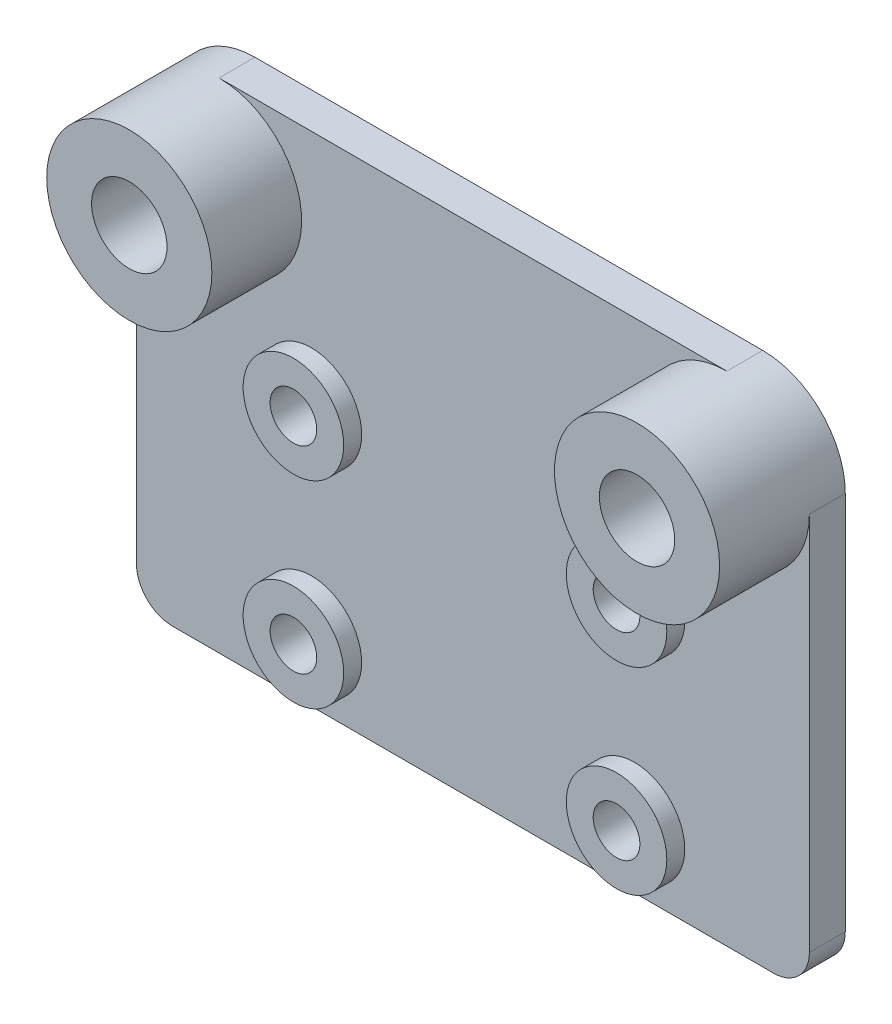
SolidWorks part; units mm, degrees
ref_plane "Plan de face" through (0, 0, 0) normal (0, 0, 1) x (1, 0, 0)
ref_plane "Plan de dessus" through (0, 0, 0) normal (0, 1, 0) x (1, 0, 0)
ref_plane "Plan de droite" through (0, 0, 0) normal (1, 0, 0) x (0, 0, -1)
sketch "Esquisse1" plane through (0, 0, 0) normal (0, 0, 1) x (1, 0, 0)
  line L0 (-14.1421, 14.1421) -> (14.1421, 14.1421) construction
  line L1 (9, 5.5) -> (-9, 5.5) construction
  line L2 (9, 5.5) -> (9, -5.5) construction
  line L3 (9, -5.5) -> (-9, -5.5) construction
  line L4 (-9, 5.5) -> (-9, -5.5) construction
  line L5 (9, 5.5) -> (-9, -5.5) construction
  line L6 (9, -5.5) -> (-9, 5.5) construction
  line L7 (14.1421, 14.1421) -> (14.1421, -14.1421) construction
  line L8 (14.1421, -14.1421) -> (-14.1421, -14.1421) construction
  line L9 (-14.1421, -14.1421) -> (-14.1421, 14.1421) construction
  circle A0 centre (0, 0) radius 20 construction
  circle A1 centre (-14.1421, 14.1421) radius 2.1
  circle A2 centre (14.1421, 14.1421) radius 2.1
  circle A3 centre (14.1421, -14.1421) radius 2.1 construction
  circle A4 centre (-14.1421, -14.1421) radius 2.1 construction
  circle A5 centre (0, 0) radius 25
  circle A6 centre (-9, 5.5) radius 1.3
  circle A7 centre (-9, -5.5) radius 1.3
  circle A8 centre (9, 5.5) radius 1.3
  circle A9 centre (9, -5.5) radius 1.3
  point P0 (0, 0)
  dimension "D3" = 40
  dimension "D4" = 4.2
  dimension "D5" = 4.2
  dimension "D6" = 4.2
  dimension "D7" = 4.2
  dimension "D8" = 50
  dimension "D9" = 2.6
  dimension "D10" = 2.6
  dimension "D11" = 2.6
  dimension "D12" = 2.6
  dimension "D1" = 18
  dimension "D2" = 11
extrude "Boss.-Extru.1" add sketch "Esquisse1" along normal blind 2
sketch "Esquisse2" plane through (0, 0, 2) normal (0, 0, 1) x (1, 0, 0)
  line L0 (0, -14) -> (0, 0) construction
  line L1 (11, -19) -> (-11, -19)
  line L2 (11, -19) -> (11, -9)
  line L3 (11, -9) -> (-11, -9)
  line L4 (-11, -19) -> (-11, -9)
  line L5 (11, -19) -> (-11, -9) construction
  line L6 (11, -9) -> (-11, -19) construction
  point P0 (0, -14)
  dimension "D1" = 9
  dimension "D2" = 22
  dimension "D3" = 10
extrude "Enlèv. mat.-Extru.1" cut sketch "Esquisse2" against normal blind 2
sketch "Esquisse3" plane through (0, 0, 2) normal (0, 0, 1) x (1, 0, 0)
  circle A0 centre (14.1421, -14.1421) radius 2.1 construction
  circle A1 centre (-14.1421, -14.1421) radius 2.1 construction
  circle A2 centre (-9, -5.5) radius 1.3 construction
  circle A3 centre (9, -5.5) radius 1.3 construction
  circle A4 centre (9, 5.5) radius 1.3 construction
  circle A5 centre (-14.1421, 14.1421) radius 2.1 construction
  circle A6 centre (-9, 5.5) radius 1.3 construction
  circle A7 centre (14.1421, -14.1421) radius 2.1
  circle A8 centre (-14.1421, -14.1421) radius 2.1
  circle A9 centre (-9, -5.5) radius 1.3
  circle A10 centre (9, -5.5) radius 1.3
  circle A11 centre (9, 5.5) radius 1.3
  circle A12 centre (-14.1421, 14.1421) radius 2.1
  circle A13 centre (-9, 5.5) radius 1.3
  circle A14 centre (-9, -5.5) radius 2.8
  circle A15 centre (9, -5.5) radius 2.8
  circle A16 centre (9, 5.5) radius 2.8
  circle A17 centre (-9, 5.5) radius 2.8
  circle A18 centre (-14.1421, 14.1421) radius 4.6
  circle A19 centre (14.1421, -14.1421) radius 3.6
  circle A20 centre (-14.1421, -14.1421) radius 3.6
  circle A21 centre (14.1421, 14.1421) radius 2.1 construction
  circle A22 centre (14.1421, 14.1421) radius 2.1
  circle A23 centre (14.1421, 14.1421) radius 4.6
  dimension "D1" = 1.5
  dimension "D2" = 2.5
  dimension "D3" = 1.5
  dimension "D4" = 2.5
extrude "Boss.-Extru.2" add sketch "Esquisse3" along normal blind 1
sketch "Esquisse4" plane through (0, 0, 0) normal (0, 0, -1) x (-1, 0, 0)
  line L0 (-14.1421, 18.7421) -> (14.1421, 18.7421)
  line L1 (-18.7421, 14.1421) -> (-18.7421, -9)
  line L2 (18.7421, 14.1421) -> (18.7421, -9)
  line L4 (18.7421, -9) -> (-18.7421, -9)
  circle A0 centre (-14.1421, 14.1421) radius 4.6 construction
  circle A1 centre (14.1421, 14.1421) radius 4.6 construction
  circle A4 centre (-14.1421, 14.1421) radius 4.6 construction
  arc A5 (-14.1421, 18.7421) -> (-18.7421, 14.1421) centre (-14.1421, 14.1421) ccw
  circle A6 centre (14.1421, 14.1421) radius 4.6 construction
  arc A7 (18.7421, 14.1421) -> (14.1421, 18.7421) centre (14.1421, 14.1421) ccw
  dimension "D1" = 9
extrude "Enlèv. mat.-Extru.2" cut sketch "Esquisse4" against normal through all flip side to cut
fillet "Congé1" radius 2 2 edges at (18.7421, -9, 1) (-18.7421, -9, 1)
sketch "Esquisse5" plane through (0, 0, 3) normal (0, 0, 1) x (1, 0, 0)
  circle A0 centre (-14.1421, -14.1421) radius 3.6 construction
  circle A1 centre (14.1421, -14.1421) radius 3.6 construction
  circle A2 centre (14.1421, 14.1421) radius 4.6 construction
  circle A3 centre (-14.1421, 14.1421) radius 4.6 construction
  circle A4 centre (-14.1421, -14.1421) radius 3.6 construction
  circle A5 centre (14.1421, -14.1421) radius 3.6 construction
  circle A6 centre (14.1421, 14.1421) radius 4.6
  circle A7 centre (-14.1421, 14.1421) radius 4.6
  circle A8 centre (14.1421, -14.1421) radius 2.1 construction
  circle A9 centre (14.1421, 14.1421) radius 2.1 construction
  circle A10 centre (-14.1421, -14.1421) radius 2.1 construction
  circle A11 centre (-14.1421, 14.1421) radius 2.1 construction
  circle A12 centre (14.1421, -14.1421) radius 2.1 construction
  circle A13 centre (14.1421, 14.1421) radius 2.1
  circle A14 centre (-14.1421, -14.1421) radius 2.1 construction
  circle A15 centre (-14.1421, 14.1421) radius 2.1
extrude "Boss.-Extru.3" add sketch "Esquisse5" along normal blind 4
